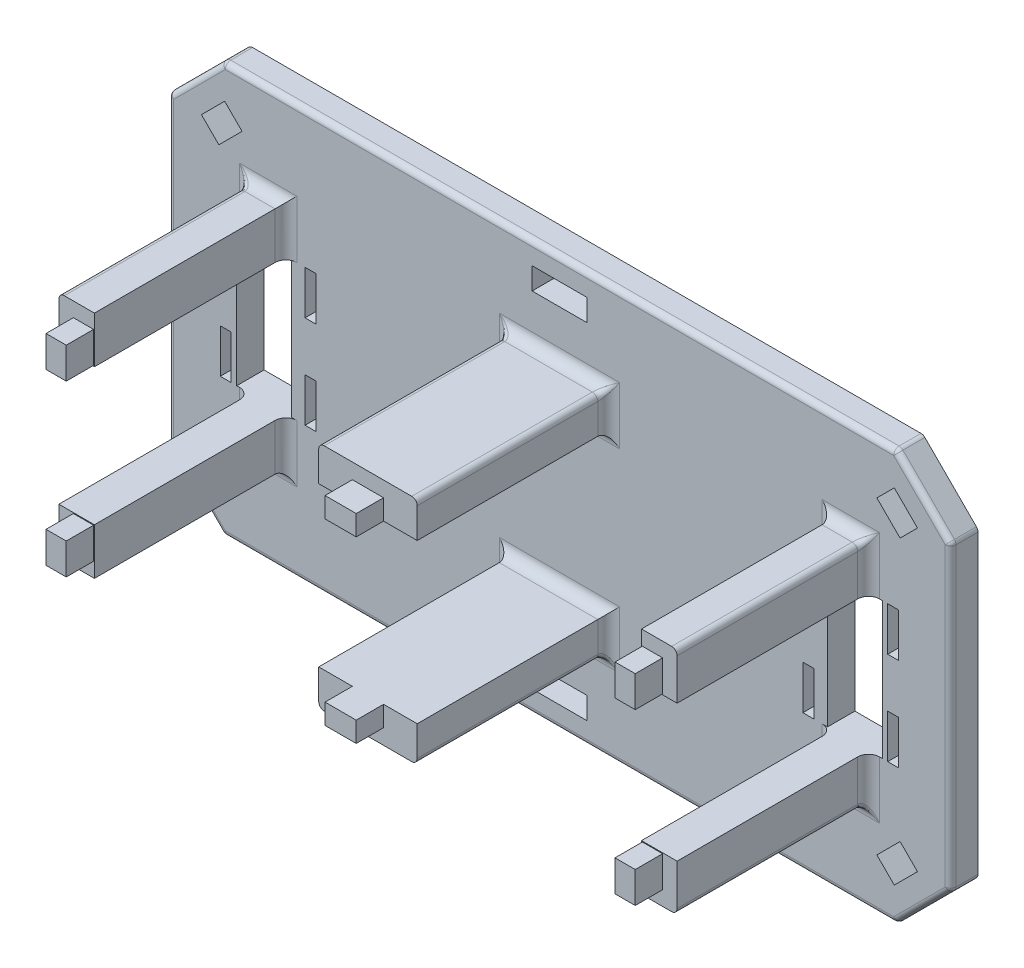
SolidWorks part; units mm, degrees
ref_plane "Plan de face" through (0, 0, 0) normal (0, 0, 1) x (1, 0, 0)
ref_plane "Plan de dessus" through (0, 0, 0) normal (0, 1, 0) x (1, 0, 0)
ref_plane "Plan de droite" through (0, 0, 0) normal (1, 0, 0) x (0, 0, -1)
sketch "Esquisse1" plane through (0, 0, 0) normal (0, 0, 1) x (1, 0, 0)
  line L0 (30, 65) -> (113, 65) construction
  line L1 (0, 0) -> (143, 0)
  line L2 (0, 0) -> (0, 75)
  line L3 (0, 75) -> (143, 75)
  line L4 (143, 0) -> (143, 75)
  line L5 (113, 65) -> (113, 10) construction
  line L6 (113, 10) -> (30, 10) construction
  line L7 (30, 10) -> (30, 65) construction
  line L9 (12.5, 50) -> (22.5, 50)
  line L10 (12.5, 50) -> (12.5, 25)
  line L11 (12.5, 25) -> (22.5, 25)
  line L12 (22.5, 50) -> (22.5, 25)
  line L13 (120.5, 50) -> (130.5, 50)
  line L14 (120.5, 50) -> (120.5, 25)
  line L15 (120.5, 25) -> (130.5, 25)
  line L16 (130.5, 50) -> (130.5, 25)
  dimension "D1" = 143
  dimension "D2" = 75
  dimension "D3" = 83
  dimension "D4" = 55
  dimension "D5" = 30
  dimension "D6" = 10
  dimension "10" = 10
  dimension "D7" = 10
  dimension "D8" = 15
  dimension "D9" = 15
  dimension "D10" = 25
  dimension "D11" = 25
  dimension "D12" = 25
  dimension "D13" = 25
extrude "Boss.-Extru.1" add sketch "Esquisse1" along normal blind 5
sketch "Esquisse2" plane through (0, 0, 5) normal (0, 0, 1) x (1, 0, 0)
  line L0 (15, 58.5) -> (128, 58.5) construction
  line L1 (128, 58.5) -> (128, 16.5) construction
  line L2 (128, 16.5) -> (15, 16.5) construction
  line L3 (15, 16.5) -> (15, 58.5) construction
  line L4 (0, 0) -> (0, 75) construction
  line L5 (0, 75) -> (143, 75) construction
  line L8 (12.5, 25) -> (22.5, 25) construction
  line L9 (15, 16.5) -> (21.5, 16.5)
  line L10 (15, 16.5) -> (15, 25)
  line L11 (15, 25) -> (21.5, 25)
  line L12 (21.5, 16.5) -> (21.5, 25)
  line L13 (12.5, 50) -> (22.5, 50) construction
  line L14 (15, 58.5) -> (21.5, 58.5)
  line L15 (15, 58.5) -> (15, 50)
  line L16 (15, 50) -> (21.5, 50)
  line L17 (21.5, 58.5) -> (21.5, 50)
  line L18 (120.5, 50) -> (130.5, 50) construction
  line L19 (128, 58.5) -> (121.5, 58.5)
  line L20 (128, 58.5) -> (128, 50)
  line L21 (128, 50) -> (121.5, 50)
  line L22 (121.5, 58.5) -> (121.5, 50)
  line L23 (120.5, 25) -> (130.5, 25) construction
  line L24 (128, 16.5) -> (121.5, 16.5)
  line L25 (128, 16.5) -> (128, 25)
  line L26 (128, 25) -> (121.5, 25)
  line L27 (121.5, 16.5) -> (121.5, 25)
  line L29 (80.5, 16.5) -> (62.5, 16.5)
  line L30 (80.5, 16.5) -> (80.5, 23)
  line L31 (80.5, 23) -> (62.5, 23)
  line L32 (62.5, 16.5) -> (62.5, 23)
  line L33 (80.5, 58.5) -> (62.5, 58.5)
  line L34 (80.5, 58.5) -> (80.5, 52)
  line L35 (80.5, 52) -> (62.5, 52)
  line L36 (62.5, 58.5) -> (62.5, 52)
  point P38 (71.5, 58.5)
  point P39 (71.5, 58.5)
  point P40 (71.5, 16.5)
  point P41 (71.5, 16.5)
  dimension "D1" = 113
  dimension "D2" = 42
  dimension "D3" = 15
  dimension "D4" = 16.5
  dimension "D5" = 6.5
  dimension "D6" = 6.5
  dimension "D7" = 6.5
  dimension "D8" = 6.5
  dimension "D9" = 6.5
  dimension "D10" = 6.5
  dimension "D11" = 18
  dimension "D12" = 18
  dimension "D13" = 0
  dimension "D14" = 0
extrude "Boss.-Extru.2" add sketch "Esquisse2" along normal blind 35
sketch "Esquisse3" plane through (0, 0, 40) normal (0, 0, 1) x (1, 0, 0)
  line L1 (21.35, 50.15) -> (17.65, 50.15)
  line L2 (21.35, 50.15) -> (21.35, 55.85)
  line L3 (21.35, 55.85) -> (17.65, 55.85)
  line L4 (17.65, 50.15) -> (17.65, 55.85)
  line L5 (21.35, 24.85) -> (17.65, 24.85)
  line L6 (21.35, 24.85) -> (21.35, 19.15)
  line L7 (21.35, 19.15) -> (17.65, 19.15)
  line L8 (17.65, 24.85) -> (17.65, 19.15)
  line L17 (12.5, 50) -> (22.5, 50) construction
  line L18 (21.5, 50) -> (21.5, 58.5) construction
  line L19 (12.5, 25) -> (22.5, 25) construction
  line L20 (21.5, 16.5) -> (21.5, 25) construction
  line L21 (71.5, 65) -> (71.5, 10) construction
  line L22 (30, 65) -> (113, 65) construction
  line L23 (113, 10) -> (30, 10) construction
  line L24 (125.35, 24.85) -> (125.35, 19.15)
  line L25 (121.65, 19.15) -> (125.35, 19.15)
  line L26 (121.65, 24.85) -> (121.65, 19.15)
  line L27 (121.65, 24.85) -> (125.35, 24.85)
  line L28 (125.35, 50.15) -> (125.35, 55.85)
  line L29 (121.65, 55.85) -> (125.35, 55.85)
  line L30 (121.65, 50.15) -> (121.65, 55.85)
  line L31 (121.65, 50.15) -> (125.35, 50.15)
  dimension "D1" = 3.7
  dimension "D2" = 5.7
  dimension "D3" = 5.7
  dimension "D4" = 0.15
  dimension "D5" = 0.15
  dimension "D6" = 3.7
  dimension "D7" = 0.15
  dimension "D8" = 0.15
extrude "Boss.-Extru.3" add sketch "Esquisse3" along normal blind 5
sketch "Esquisse5" plane through (0, 0, 40) normal (0, 0, 1) x (1, 0, 0)
  line L0 (62.5, 52) -> (80.5, 52) construction
  line L1 (68.65, 52) -> (74.35, 52)
  line L2 (68.65, 52) -> (68.65, 55.7)
  line L3 (68.65, 55.7) -> (74.35, 55.7)
  line L4 (74.35, 52) -> (74.35, 55.7)
  line L5 (80.5, 23) -> (62.5, 23) construction
  line L6 (68.65, 23) -> (74.35, 23)
  line L7 (68.65, 23) -> (68.65, 19.3)
  line L8 (68.65, 19.3) -> (74.35, 19.3)
  line L9 (74.35, 23) -> (74.35, 19.3)
  line L10 (80.5, 23) -> (62.5, 23) construction
  point P13 (71.5, 52)
  point P14 (71.5, 52)
  point P19 (71.5, 23)
  point P20 (71.5, 23)
  dimension "D1" = 3.7
  dimension "D2" = 5.7
  dimension "D3" = 0
  dimension "D4" = 5.7
  dimension "D5" = 3.7
  dimension "D6" = 0
extrude "Boss.-Extru.4" add sketch "Esquisse5" along normal blind 5
fillet "Congé1" radius 2 20 edges at (121.5, 54.25, 5) (121.5, 20.75, 5) (124.75, 16.5, 5) (128, 20.75, 5) (18.25, 16.5, 5) (15, 20.75, 5) (71.5, 16.5, 5) (62.5, 19.75, 5) (71.5, 52, 5) (62.5, 55.25, 5) (128, 54.25, 5) (124.75, 58.5, 5) (71.5, 23, 5) (80.5, 19.75, 5) (80.5, 55.25, 5) (71.5, 58.5, 5) (21.5, 20.75, 5) (21.5, 54.25, 5) (18.25, 58.5, 5) (15, 54.25, 5)
sketch "Esquisse6" plane through (0, 0, 5) normal (0, 0, 1) x (1, 0, 0)
  line L0 (12.5, 50) -> (22.5, 50) construction
  line L1 (25, 50) -> (27, 50)
  line L2 (25, 50) -> (25, 42)
  line L3 (25, 42) -> (27, 42)
  line L4 (27, 50) -> (27, 42)
  line L5 (25, 33) -> (27, 33)
  line L6 (25, 33) -> (25, 25)
  line L7 (25, 25) -> (27, 25)
  line L8 (27, 33) -> (27, 25)
  line L9 (12.5, 25) -> (22.5, 25) construction
  line L10 (22.5, 50) -> (22.5, 25) construction
  line L11 (71.5, 55.7) -> (71.5, 19.3) construction
  line L12 (74.35, 55.7) -> (68.65, 55.7) construction
  line L13 (68.65, 19.3) -> (74.35, 19.3) construction
  line L22 (18.25, 58.5) -> (18.25, 16.5) construction
  line L23 (21.5, 58.5) -> (15, 58.5) construction
  line L24 (15, 16.5) -> (21.5, 16.5) construction
  line L25 (9.5, 33) -> (9.5, 25)
  line L26 (11.5, 25) -> (9.5, 25)
  line L27 (11.5, 33) -> (11.5, 25)
  line L28 (11.5, 33) -> (9.5, 33)
  line L29 (9.5, 50) -> (9.5, 42)
  line L30 (11.5, 42) -> (9.5, 42)
  line L31 (11.5, 50) -> (11.5, 42)
  line L32 (11.5, 50) -> (9.5, 50)
  line L33 (25, 50) -> (27, 50)
  line L34 (25, 50) -> (25, 42)
  line L35 (25, 42) -> (27, 42)
  line L36 (27, 50) -> (27, 42)
  line L37 (25, 33) -> (27, 33)
  line L38 (25, 33) -> (25, 25)
  line L39 (25, 25) -> (27, 25)
  line L40 (27, 33) -> (27, 25)
  line L41 (9.5, 33) -> (9.5, 25)
  line L42 (11.5, 25) -> (9.5, 25)
  line L43 (11.5, 33) -> (11.5, 25)
  line L44 (11.5, 33) -> (9.5, 33)
  line L45 (9.5, 50) -> (9.5, 42)
  line L46 (11.5, 42) -> (9.5, 42)
  line L47 (11.5, 50) -> (11.5, 42)
  line L48 (11.5, 50) -> (9.5, 50)
  line L49 (124.75, 58.5) -> (124.75, 16.5) construction
  line L50 (131.5, 50) -> (133.5, 50)
  line L51 (131.5, 50) -> (131.5, 42)
  line L52 (131.5, 42) -> (133.5, 42)
  line L53 (133.5, 50) -> (133.5, 42)
  line L54 (131.5, 33) -> (133.5, 33)
  line L55 (131.5, 33) -> (131.5, 25)
  line L56 (131.5, 25) -> (133.5, 25)
  line L57 (133.5, 33) -> (133.5, 25)
  line L58 (116, 33) -> (116, 25)
  line L59 (118, 25) -> (116, 25)
  line L60 (118, 33) -> (118, 25)
  line L61 (118, 33) -> (116, 33)
  line L62 (116, 50) -> (116, 42)
  line L63 (118, 42) -> (116, 42)
  line L64 (118, 50) -> (118, 42)
  line L65 (118, 50) -> (116, 50)
  line L66 (131.5, 50) -> (133.5, 50)
  line L67 (131.5, 50) -> (131.5, 42)
  line L68 (131.5, 42) -> (133.5, 42)
  line L69 (133.5, 50) -> (133.5, 42)
  line L70 (131.5, 33) -> (133.5, 33)
  line L71 (131.5, 33) -> (131.5, 25)
  line L72 (131.5, 25) -> (133.5, 25)
  line L73 (133.5, 33) -> (133.5, 25)
  line L74 (116, 33) -> (116, 25)
  line L75 (118, 25) -> (116, 25)
  line L76 (118, 33) -> (118, 25)
  line L77 (118, 33) -> (116, 33)
  line L78 (116, 50) -> (116, 42)
  line L79 (118, 42) -> (116, 42)
  line L80 (118, 50) -> (118, 42)
  line L81 (118, 50) -> (116, 50)
  dimension "D1" = 8
  dimension "D2" = 8
  dimension "D3" = 2
  dimension "D4" = 2
  dimension "D5" = 2.5
  dimension "D6" = 2.5
extrude "Enlèv. mat.-Extru.3" cut sketch "Esquisse6" against normal blind 5 contours L31 L32 L29 L30 | L4 L1 L2 L3 | L8 L5 L6 L7 | L27 L28 L25 L26 | L64 L65 L62 L63 | L53 L50 L51 L52 | L57 L54 L55 L56 | L60 L61 L58 L59 region at (26, 46, 5) region at (26, 29, 5) region at (10.5, 29, 5) region at (10.5, 46, 5) region at (132.5, 46, 5) region at (132.5, 29, 5) region at (117, 29, 5) region at (117, 46, 5)
chamfer "Chanfrein1" distance 10 angle 45 4 edges at (143, 75, 2.5) (0, 75, 2.5) (0, 0, 2.5) (143, 0, 2.5)
sketch "Esquisse7" plane through (0, 0, 0) normal (0, 0, -1) x (-1, 0, 0)
  line L0 (-143, 10) -> (-133, 0) construction
  line L1 (-143, 10) -> (-136.636, 16.364) construction
  line L2 (-133, 0) -> (-126.636, 6.364) construction
  line L3 (-136.636, 16.364) -> (-126.636, 6.364) construction
  line L4 (-136.9393, 10.3033) -> (-132.6967, 6.0607)
  line L5 (-136.9393, 10.3033) -> (-133.7574, 13.4853)
  line L6 (-132.6967, 6.0607) -> (-129.5147, 9.2426)
  line L7 (-133.7574, 13.4853) -> (-129.5147, 9.2426)
  line L8 (-143, 37.5) -> (0, 37.5) construction
  line L9 (-143, 0) -> (-143, 75) construction
  line L10 (0, 0) -> (0, 75) construction
  line L11 (-136.636, 58.636) -> (-126.636, 68.636) construction
  line L12 (-133, 75) -> (-126.636, 68.636) construction
  line L13 (-143, 65) -> (-136.636, 58.636) construction
  line L14 (-143, 65) -> (-133, 75) construction
  line L15 (-133.7574, 61.5147) -> (-129.5147, 65.7574)
  line L16 (-132.6967, 68.9393) -> (-129.5147, 65.7574)
  line L17 (-136.9393, 64.6967) -> (-133.7574, 61.5147)
  line L18 (-136.9393, 64.6967) -> (-132.6967, 68.9393)
  line L19 (-71.5, 75) -> (-71.5, 0) construction
  line L20 (0, 75) -> (-143, 75) construction
  line L21 (0, 0) -> (-143, 0) construction
  line L22 (-6.364, 16.364) -> (-16.364, 6.364) construction
  line L23 (-10, 0) -> (-16.364, 6.364) construction
  line L24 (0, 10) -> (-6.364, 16.364) construction
  line L25 (0, 10) -> (-10, 0) construction
  line L26 (-9.2426, 13.4853) -> (-13.4853, 9.2426)
  line L27 (-10.3033, 6.0607) -> (-13.4853, 9.2426)
  line L28 (-6.0607, 10.3033) -> (-9.2426, 13.4853)
  line L29 (-6.0607, 10.3033) -> (-10.3033, 6.0607)
  line L30 (0, 65) -> (-10, 75) construction
  line L31 (0, 65) -> (-6.364, 58.636) construction
  line L32 (-10, 75) -> (-16.364, 68.636) construction
  line L33 (-6.364, 58.636) -> (-16.364, 68.636) construction
  line L34 (-6.0607, 64.6967) -> (-10.3033, 68.9393)
  line L35 (-6.0607, 64.6967) -> (-9.2426, 61.5147)
  line L36 (-10.3033, 68.9393) -> (-13.4853, 65.7574)
  line L37 (-9.2426, 61.5147) -> (-13.4853, 65.7574)
  line L38 (-86.5, 0) -> (-86.5, 8) construction
  line L39 (-86.5, 8) -> (-56.5, 8) construction
  line L40 (-56.5, 8) -> (-56.5, 0) construction
  line L41 (-86.5, 0) -> (-56.5, 0) construction
  line L42 (-76.5, 67) -> (-66.5, 71) construction
  line L43 (-76.5, 4) -> (-66.5, 4)
  line L44 (-76.5, 4) -> (-76.5, 8)
  line L45 (-76.5, 8) -> (-66.5, 8)
  line L46 (-66.5, 4) -> (-66.5, 8)
  line L47 (-76.5, 4) -> (-66.5, 8) construction
  line L48 (-76.5, 8) -> (-66.5, 4) construction
  line L49 (-76.5, 71) -> (-66.5, 67) construction
  line L51 (-66.5, 71) -> (-66.5, 67)
  line L52 (-76.5, 67) -> (-66.5, 67)
  line L53 (-76.5, 71) -> (-76.5, 67)
  line L54 (-76.5, 71) -> (-66.5, 71)
  point P12 (-131.636, 11.364)
  point P13 (-131.636, 11.364)
  point P26 (-131.636, 63.636)
  point P41 (-11.364, 11.364)
  point P50 (-11.364, 63.636)
  point P53 (-71.5, 6)
  point P66 (-71.5, 69)
  dimension "D1" = 9
  dimension "D2" = 6
  dimension "D4" = 10
  dimension "D5" = 4.5
  dimension "D6" = 0
  dimension "4" = 4
  dimension "D7" = 30
  dimension "D8" = 15
  dimension "D9" = 8
extrude "Enlèv. mat.-Extru.4" cut sketch "Esquisse7" against normal blind 5
fillet "Congé2" radius 1 32 edges at (61.9142, 15.9142, 5.5858) (81.0858, 15.9142, 5.5858) (81.0858, 59.0858, 5.5858) (61.9142, 59.0858, 5.5858) (14.4142, 15.9142, 5.5858) (14.4142, 59.0858, 5.5858) (128.5858, 59.0858, 5.5858) (128.5858, 15.9142, 5.5858) (62.5, 16.5, 23.5) (80.5, 16.5, 23.5) (80.5, 58.5, 23.5) (62.5, 58.5, 23.5) (15, 16.5, 23.5) (15, 58.5, 23.5) (128, 58.5, 23.5) (128, 16.5, 23.5) (138, 5, 5) (71.5, 0, 5) (5, 5, 5) (0, 37.5, 5) (5, 70, 5) (71.5, 75, 5) (138, 70, 5) (143, 37.5, 5) (143, 65, 2.5) (133, 75, 2.5) (10, 75, 2.5) (0, 65, 2.5) (0, 10, 2.5) (10, 0, 2.5) (133, 0, 2.5) (143, 10, 2.5)
